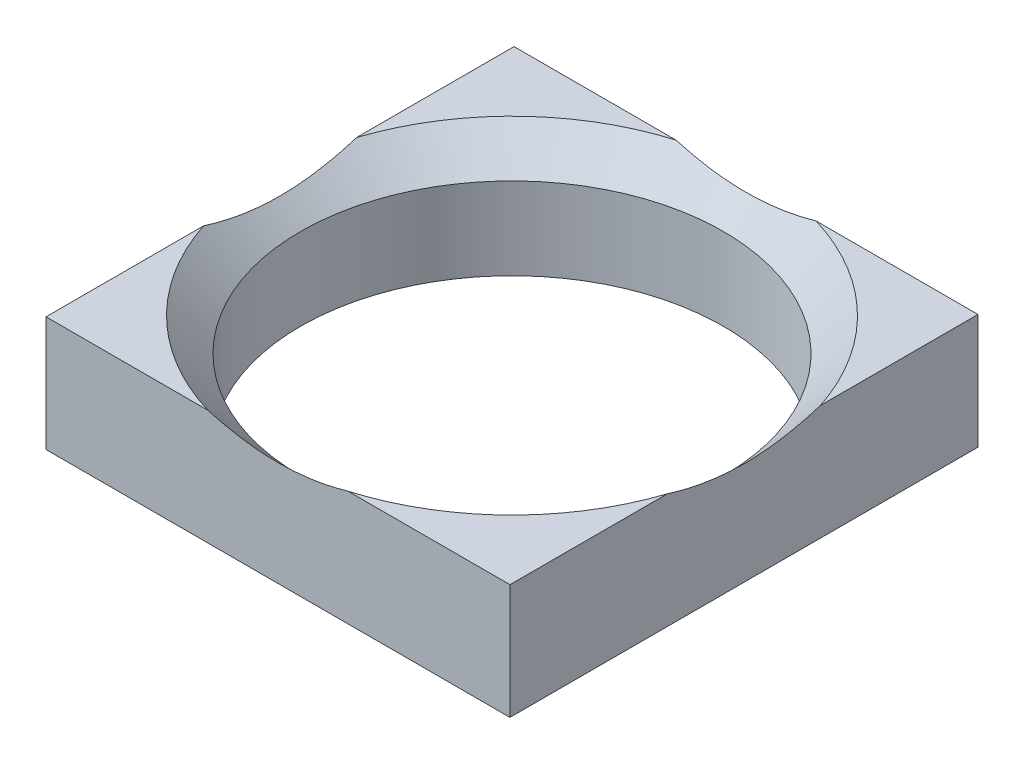
SolidWorks part; units mm, degrees
ref_plane "前视基准面" through (0, 0, 0) normal (0, 0, 1) x (1, 0, 0)
ref_plane "上视基准面" through (0, 0, 0) normal (0, 1, 0) x (1, 0, 0)
ref_plane "右视基准面" through (0, 0, 0) normal (1, 0, 0) x (0, 0, -1)
other "Configuration Table"
sketch "草图1" plane through (0, 0, 0) normal (0, 1, 0) x (1, 0, 0)
  line L1 (-5.95, 5.95) -> (5.95, 5.95)
  line L2 (-5.95, 5.95) -> (-5.95, -5.95)
  line L3 (-5.95, -5.95) -> (5.95, -5.95)
  line L4 (5.95, 5.95) -> (5.95, -5.95)
  line L5 (-5.95, 5.95) -> (5.95, -5.95) construction
  line L6 (-5.95, -5.95) -> (5.95, 5.95) construction
  circle A0 centre (0, 0) radius 5.05
  point P0 (0, 0)
  dimension "D1" = 10.1
  dimension "D2" = 11.9
extrude "凸台-拉伸1" add sketch "草图1" along normal blind 2.8
chamfer "倒角1" distance 0.9 angle 45 1 edges at (0, 2.8, 5.05)
sketch "Sketch1" plane through (0, 2.8, 0) normal (0, 1, 0) x (1, 0, 0)
  line L1 (-5.65, 5.7) -> (5.65, 5.7)
  line L2 (-5.65, 5.7) -> (-5.65, -5.7)
  line L3 (-5.65, -5.7) -> (5.65, -5.7)
  line L4 (5.65, 5.7) -> (5.65, -5.7)
  line L5 (-5.65, 5.7) -> (5.65, -5.7) construction
  line L6 (-5.65, -5.7) -> (5.65, 5.7) construction
  point P0 (0, 0)
  dimension "D1" = 11.4
  dimension "D2" = 11.3
extrude "Cut-Extrude1" cut sketch "Sketch1" against normal through all flip side to cut
sketch "Sketch2" plane through (0, 2.8, 0) normal (0, 1, 0) x (1, 0, 0)
  circle A0 centre (0, 0) radius 5.15
  dimension "D1" = 10.3
extrude "Cut-Extrude2" cut sketch "Sketch2" against normal through all
